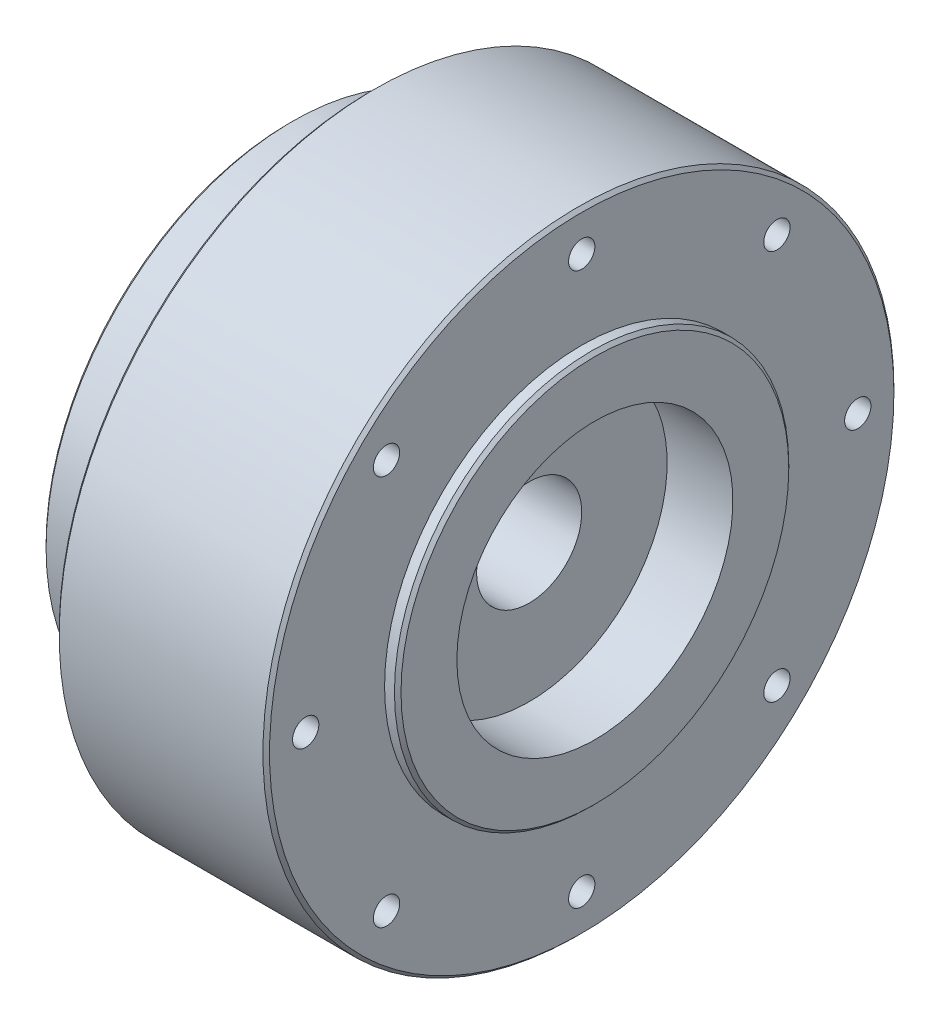
SolidWorks part; units mm, degrees
ref_plane "Front Plane" through (0, 0, 0) normal (0, 0, 1) x (1, 0, 0)
ref_plane "Top Plane" through (0, 0, 0) normal (0, 1, 0) x (1, 0, 0)
ref_plane "Right Plane" through (0, 0, 0) normal (1, 0, 0) x (0, 0, -1)
ref_axis "Axis1" through (65.3475, 0, 0) along (-1, 0, 0)
sketch "Sketch2" plane through (0, 0, 0) normal (0, 1, 0) x (1, 0, 0)
  line L0 (0, 0) -> (30.917, 0) construction
  line L1 (-44.2539, 0) -> (44.2539, 0) construction
  line L3 (0, -44.7868) -> (0, 44.7868) construction
  line L4 (0, 48) -> (-32, 48)
  line L5 (-32, 48) -> (-32, 37.5)
  line L6 (-32, 37.5) -> (-44.5, 37.5)
  line L9 (0, 48) -> (0, 30)
  line L10 (0, 30) -> (2, 30)
  line L11 (2, 30) -> (2, 21)
  line L12 (2, 0) -> (0, 0)
  line L13 (0, 0) -> (2, 0)
  line L14 (-42.5, 11) -> (-36.5, 11)
  line L15 (-36.5, 11) -> (-36.5, 8)
  line L16 (-36.5, 8) -> (-8, 8)
  line L17 (-8, 8) -> (-8, 21)
  line L18 (-8, 21) -> (2, 21)
  line L19 (-32, 0) -> (39.088, 0) construction
  line L21 (-44.5, 0) -> (-42.5, 0)
  line L22 (-42.5, 0) -> (-42.5, 11)
  line L23 (-44.5, 0) -> (-44.5, 37.5)
  dimension "D1" = 48
  dimension "D2" = 12.5
  dimension "D3" = 32
  dimension "D4" = 2
  dimension "D5" = 30
  dimension "D6" = 37.5
  dimension "D7" = 21
  dimension "D8" = 10
  dimension "D9" = 8
  dimension "D10" = 6
  dimension "D11" = 11
  dimension "D12" = 2
revolve "Revolve1" add sketch "Sketch2" angle 360 about L19 region at (-21.8713, 0, -27.5977)
sketch "Sketch3" plane through (-32, 0, 0) normal (-1, 0, 0) x (0, 0, 1)
  line L0 (0, -44.2539) -> (0, 44.2539) construction
  line L1 (55, 0) -> (-55, 0) construction
  circle A0 centre (0, 42) radius 2
  dimension "D1" = 4
  dimension "D2" = 42
extrude "Cut-Extrude1" cut sketch "Sketch3" against normal up to surface (32 mm away) up to face at (0, 0, 30)
pattern_circular "CirPattern1" count 8 over 360 about axis through (65.3475, 0, 0) along (-1, 0, 0) of "Cut-Extrude1"
chamfer "Chamfer1" distance 0.5 angle 45 3 edges at (-44.5, 0, 37.5) (-32, 0, 48) (0, 0, 48)
chamfer "Chamfer2" distance 0.5 angle 45 1 edges at (2, 0, 30)
